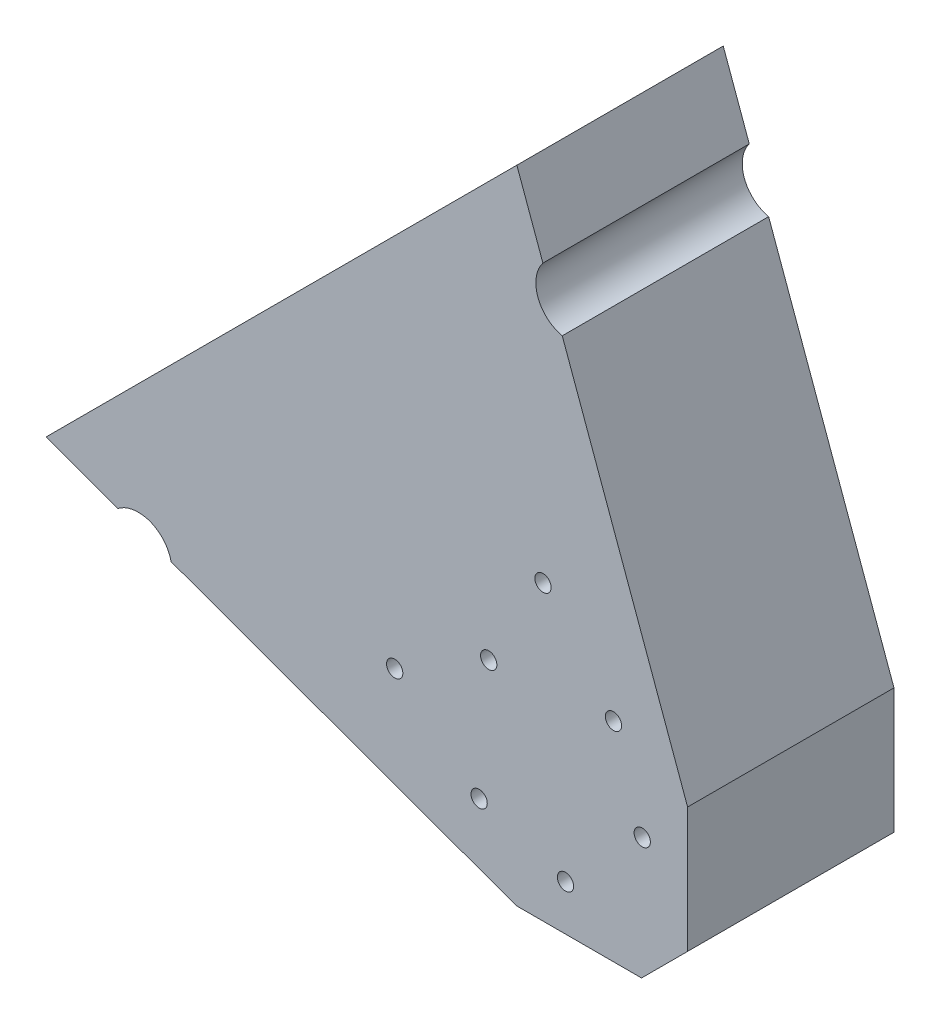
SolidWorks part; units mm, degrees
ref_plane "Front Plane" through (0, 0, 0) normal (0, 0, 1) x (1, 0, 0)
ref_plane "Top Plane" through (0, 0, 0) normal (0, 1, 0) x (1, 0, 0)
ref_plane "Right Plane" through (0, 0, 0) normal (1, 0, 0) x (0, 0, -1)
sketch "Sketch1" plane through (0, 0, 0) normal (0, 0, 1) x (1, 0, 0)
  line L0 (0, 0) -> (0, 128.66) construction
  line L1 (-151.66, -48) -> (-128.66, -48) construction
  line L2 (-151.66, -48) -> (-151.66, 52) construction
  line L4 (-128.66, -48) -> (-128.66, 27) construction
  line L5 (-52, 151.66) -> (48, 151.66) construction
  line L7 (-27, 128.66) -> (48, 128.66) construction
  line L8 (48, 151.66) -> (48, 128.66) construction
  line L9 (0, 0) -> (-128.66, 0) construction
  line L10 (-27, 128.66) -> (-128.66, 27) construction
  line L11 (-128.66, 128.66) -> (-27, 128.66) construction
  line L12 (-128.66, 27) -> (-128.66, 128.66) construction
  line L13 (-58.4584, 145.2016) -> (-145.2016, 58.4584)
  line L14 (-151.66, 151.66) -> (-52, 151.66) construction
  line L15 (-151.66, 52) -> (-151.66, 151.66) construction
  line L16 (-24.3179, 128.66) -> (-25, 128.66) construction
  line L17 (23.2069, 128.66) -> (48, 128.66) construction
  line L18 (-128.66, 25) -> (-128.66, 24.3179) construction
  line L19 (-128.66, -48) -> (-128.66, -23.2069) construction
  line L20 (-128.66, 23.2069) -> (-128.66, -23.2069) construction
  line L21 (-23.2069, 128.66) -> (23.2069, 128.66) construction
  line L22 (-58.5251, 27) -> (-35.4853, 27)
  line L23 (-27, 35.4853) -> (-27, 58.5251)
  line L24 (-35.4853, 27) -> (-27, 35.4853)
  line L25 (-25, 128.66) -> (-27, 128.66) construction
  line L26 (-27, 126.66) -> (-27, 128.66) construction
  line L27 (-128.66, 27) -> (-128.66, 25) construction
  line L28 (-128.66, 27) -> (-126.66, 27) construction
  line L29 (-23.2069, 128.66) -> (-24.3179, 128.66) construction
  line L30 (-128.66, 24.3179) -> (-128.66, 23.2069) construction
  line L31 (-27, 126.66) -> (-27, 128.66) construction
  line L32 (-27, 151.66) -> (-52, 151.66) construction
  line L33 (-126.66, 27) -> (-128.66, 27) construction
  line L34 (-151.66, 52) -> (-151.66, 27) construction
  line L35 (-27, 58.5251) -> (-50.0954, 122.1593)
  line L36 (-52, 151.66) -> (-58.4584, 145.2016) construction
  line L37 (-27, 128.66) -> (-27, 151.66) construction
  line L38 (-27, 58.5251) -> (-27, 126.66) construction
  line L39 (0, 0) -> (-80.9943, 80.9943) construction
  line L40 (-58.5251, 27) -> (-122.1593, 50.0954)
  line L41 (-126.66, 27) -> (-58.5251, 27) construction
  line L42 (-145.2016, 58.4584) -> (-151.66, 52) construction
  line L43 (-128.66, 27) -> (-151.66, 27) construction
  line L44 (-53.6593, 131.9788) -> (-58.4584, 145.2016)
  line L47 (-131.9788, 53.6593) -> (-145.2016, 58.4584)
  line L48 (-109.9836, 45.6764) -> (-131.9788, 53.6593) construction
  line L49 (-122.1593, 50.0954) -> (-109.9836, 45.6764) construction
  arc A0 (23.2069, 128.66) -> (-22.3981, 129.3547) centre (0, 102.46) ccw construction
  arc A1 (-129.3547, 22.3981) -> (-128.66, -23.2069) centre (-102.46, 0) ccw construction
  arc A2 (-25, 128.66) -> (-27, 126.66) centre (-25, 126.66) ccw construction
  arc A3 (-126.66, 27) -> (-128.66, 25) centre (-126.66, 25) ccw construction
  arc A4 (-24.3179, 128.66) -> (-22.3981, 129.3547) centre (-24.3179, 131.66) ccw construction
  arc A5 (-22.3981, 129.3547) -> (-23.2069, 128.66) centre (0, 102.46) ccw construction
  arc A6 (-128.66, 24.3179) -> (-129.3547, 22.3981) centre (-131.66, 24.3179) cw construction
  arc A7 (-128.66, 23.2069) -> (-129.3547, 22.3981) centre (-102.46, 0) ccw construction
  arc A8 (-53.6593, 131.9788) -> (-50.0954, 122.1593) centre (-48.7855, 128.1912) ccw
  arc A9 (-131.9788, 53.6593) -> (-122.1593, 50.0954) centre (-128.1912, 48.7855) cw
  dimension "D6" = 35
  dimension "D10" = 2
  dimension "D11" = 3
  dimension "D1" = 135
  dimension "D2" = 23
  dimension "D3" = 128.66
  dimension "D4" = 48
  dimension "D8" = 27
  dimension "D9" = 12
  dimension "D5" = 100
  dimension "D7" = 26.2
extrude "Boss-Extrude1" add sketch "Sketch1" along normal blind 38.0226
ref_axis "Axis1" through (0, 0, -1.9011) along (0, 0, 1)
sketch "Sketch4" plane through (0, 0, 38.0226) normal (0, 0, 1) x (1, 0, 0)
  line L0 (0, 0) -> (0, 52.0101) construction
  line L1 (0, 0) -> (-63.6396, 63.6396) construction
  line L2 (0, 0) -> (-52.0101, 0) construction
  line L5 (-80.9601, 53.6396) -> (-63.6396, 63.6396) construction
  line L6 (-63.6396, 63.6396) -> (-83.2677, 83.2677) construction
  line L8 (-65.4074, 40.6586) -> (-40.6586, 65.4074) construction
  line L9 (-35.3553, 49.4975) -> (-49.4975, 35.3553) construction
  line L11 (-35.4853, 27) -> (-27, 35.4853) construction
  circle A1 centre (-63.6396, 63.6396) radius 1.5
  circle A3 centre (-80.9601, 53.6396) radius 1.5
  circle A4 centre (-53.6396, 80.9601) radius 1.5
  circle A9 centre (-40.6586, 65.4074) radius 1.5
  circle A10 centre (-65.4074, 40.6586) radius 1.5
  circle A11 centre (-49.4975, 35.3553) radius 1.5
  circle A12 centre (-35.3553, 49.4975) radius 1.5
  dimension "D2" = 20
  dimension "D3" = 3
  dimension "D1" = 45
  dimension "D6" = 45.8162
  dimension "D7" = 75
  dimension "D9" = 35
  dimension "D10" = 20
  dimension "D11" = 15
  dimension "D12" = 15
extrude "Cut-Extrude2" cut sketch "Sketch4" against normal through all
equation "\"EyeDiameter\" = 155"
equation "\"BasePlaneDistance\" = \"EyeDiameter\"/2+15"
equation "\"EyeClearance\" = 2"
equation "\"L2Thickness\" = 15"
equation "\"L2_ID\" = 20"
equation "\"Offset\"= - 2"
equation "\"D3@Sketch1\"=\"BasePlaneDistance\" + 38.16 +\"Offset\""
equation "\"D7@Sketch1\"=24.20 - \"Offset\""
equation "\"D2@Sketch1\"=25.00 + \"Offset\""
